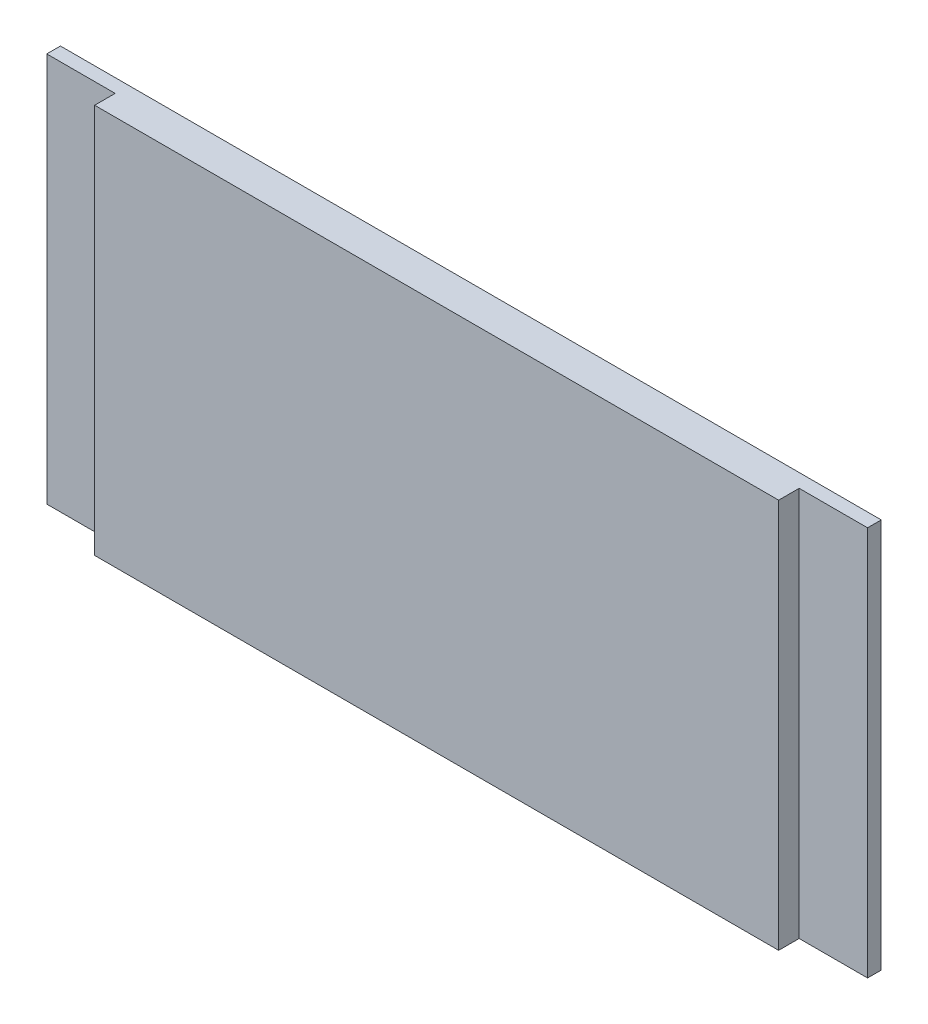
SolidWorks part; units mm, degrees
ref_plane "Front Plane" through (0, 0, 0) normal (0, 0, 1) x (1, 0, 0)
ref_plane "Top Plane" through (0, 0, 0) normal (0, 1, 0) x (1, 0, 0)
ref_plane "Right Plane" through (0, 0, 0) normal (1, 0, 0) x (0, 0, -1)
sketch "Sketch1" plane through (0, 0, 0) normal (0, 0, 1) x (1, 0, 0)
  line L1 (-60, -28.5) -> (60, -28.5)
  line L2 (-60, -28.5) -> (-60, 28.5)
  line L3 (-60, 28.5) -> (60, 28.5)
  line L4 (60, -28.5) -> (60, 28.5)
  line L5 (-60, -28.5) -> (60, 28.5) construction
  line L6 (-60, 28.5) -> (60, -28.5) construction
  line L7 (-50, -28.5) -> (50, -28.5)
  line L8 (-50, -28.5) -> (-50, 28.5)
  line L9 (-50, 28.5) -> (50, 28.5)
  line L10 (50, -28.5) -> (50, 28.5)
  line L11 (-50, -28.5) -> (50, 28.5) construction
  line L12 (-50, 28.5) -> (50, -28.5) construction
  point P0 (0, 0)
  point P6 (0, 0)
  dimension "D1" = 120
  dimension "D2" = 57
  dimension "D3" = 100
extrude "Boss-Extrude1" add sketch "Sketch1" along normal blind 5 contours L1 L10 L3 L8 region at (0, 0, 0)
extrude "Boss-Extrude2" add sketch "Sketch1<3>" along normal blind 2 contours L1 L8 L3 L2 | L10 L1 L4 L3 region at (-55, 0, 0) region at (55, 0, 0)
sketch "Sketch1<3>" plane through (0, 0, 0) normal (0, 0, 1) x (1, 0, 0) same geometry as "Sketch1"
